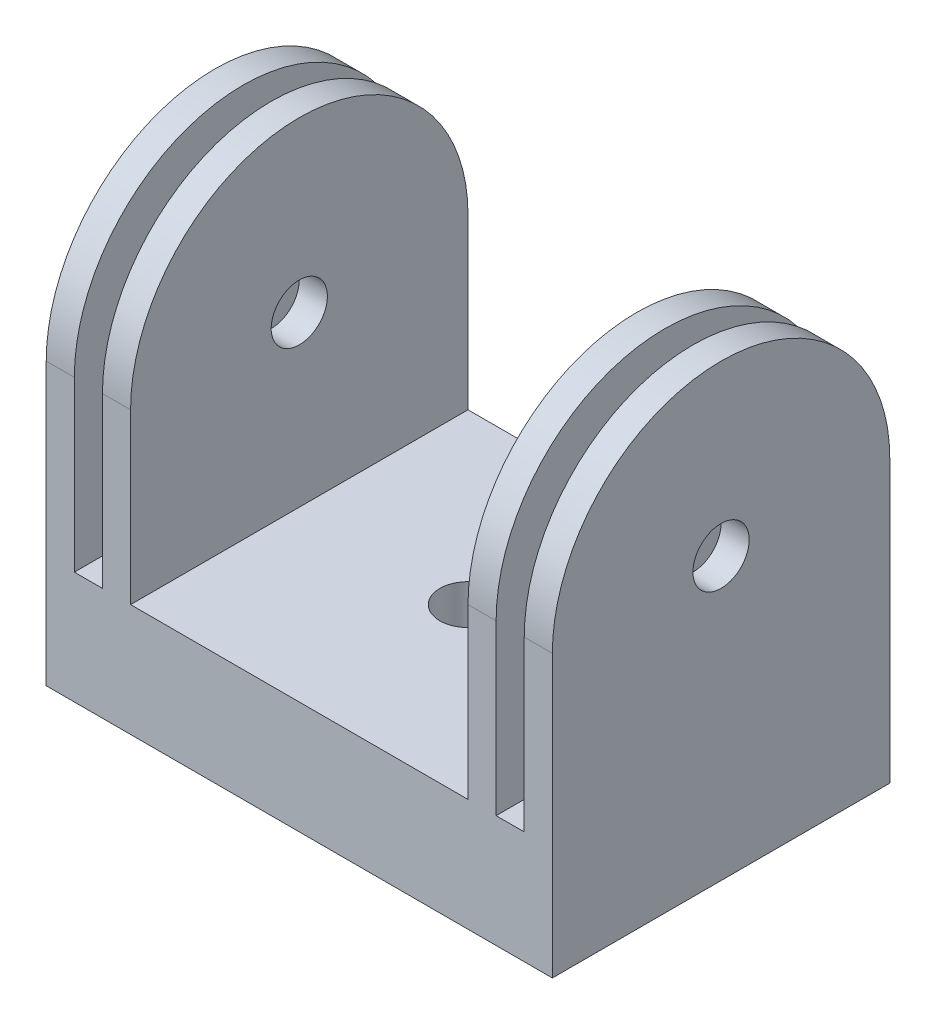
SolidWorks part; units mm, degrees
material "6061 Alloy"
ref_plane "Front Plane" through (0, 0, 0) normal (0, 0, 1) x (1, 0, 0)
ref_plane "Top Plane" through (0, 0, 0) normal (0, 1, 0) x (1, 0, 0)
ref_plane "Right Plane" through (0, 0, 0) normal (1, 0, 0) x (0, 0, -1)
sketch "Sketch1" plane through (0, 0, 0) normal (0, 1, 0) x (1, 0, 0)
  line L1 (-22.5, 15) -> (22.5, 15)
  line L2 (-22.5, 15) -> (-22.5, -15)
  line L3 (-22.5, -15) -> (22.5, -15)
  line L4 (22.5, 15) -> (22.5, -15)
  line L5 (0, -15) -> (0, 15) construction
  line L6 (-22.5, 0) -> (22.5, 0) construction
  point P0 (0, 0)
  dimension "D1" = 45
  dimension "D2" = 30
extrude "Boss-Extrude1" add sketch "Sketch1" along normal blind 10
sketch "Sketch2" plane through (22.5, 0, 0) normal (1, 0, 0) x (0, 0, -1)
  line L0 (15, 10) -> (15, 0) construction
  line L1 (-15, 10) -> (15, 10)
  line L2 (-15, 10) -> (-15, 25)
  line L4 (15, 10) -> (15, 25)
  arc A0 (-15, 25) -> (15, 25) centre (0, 25) cw
  circle A1 centre (0, 25) radius 2.5
  dimension "D2" = 5
  dimension "D4" = 15
  dimension "D1" = 15
  dimension "D3" = 10
extrude "Boss-Extrude2" add sketch "Sketch2" against normal blind 2.5
ref_plane "Plane1" through (18.75, 0, 0) normal (1, 0, 0) x (0, 0, -1)
mirror "Mirror2" about plane through (18.75, 0, 0) normal (1, 0, 0) of "Boss-Extrude2"
mirror "Mirror3" about plane through (0, 0, 0) normal (1, 0, 0) of "Mirror2"
hole_wizard "M6x1.0 Tapped Hole1" positions "Sketch3" profile "Sketch4" tap size "M6x1.0" standard "ANSI Metric" end condition through all
sketch "Sketch3" plane through (0, 0, 0) normal (0, -1, 0) x (-1, 0, 0)
  line L0 (22.5, 0) -> (-22.5, 0) construction
  line L1 (22.5, 15) -> (22.5, -15) construction
  line L2 (-22.5, 15) -> (-22.5, -15) construction
  point P7 (0, 0)
sketch "Sketch4" plane through (0, 0, 0) normal (1, 0, 0) x (0, 0, -1)
  line L0 (0, 0) -> (0, 40)
  line L1 (0, 40) -> (2.5, 40)
  line L2 (2.5, 40) -> (2.5, 0)
  line L5 (2.5, 0) -> (0, 0)
  line L11 (0, -6.35) -> (0, 107.95) construction
  dimension "Thru Tap Drill Dia." = 5
  dimension "Thru Tap Drill Depth" = 40
cosmetic thread "Hole Thread1" parameters "D2"=6
